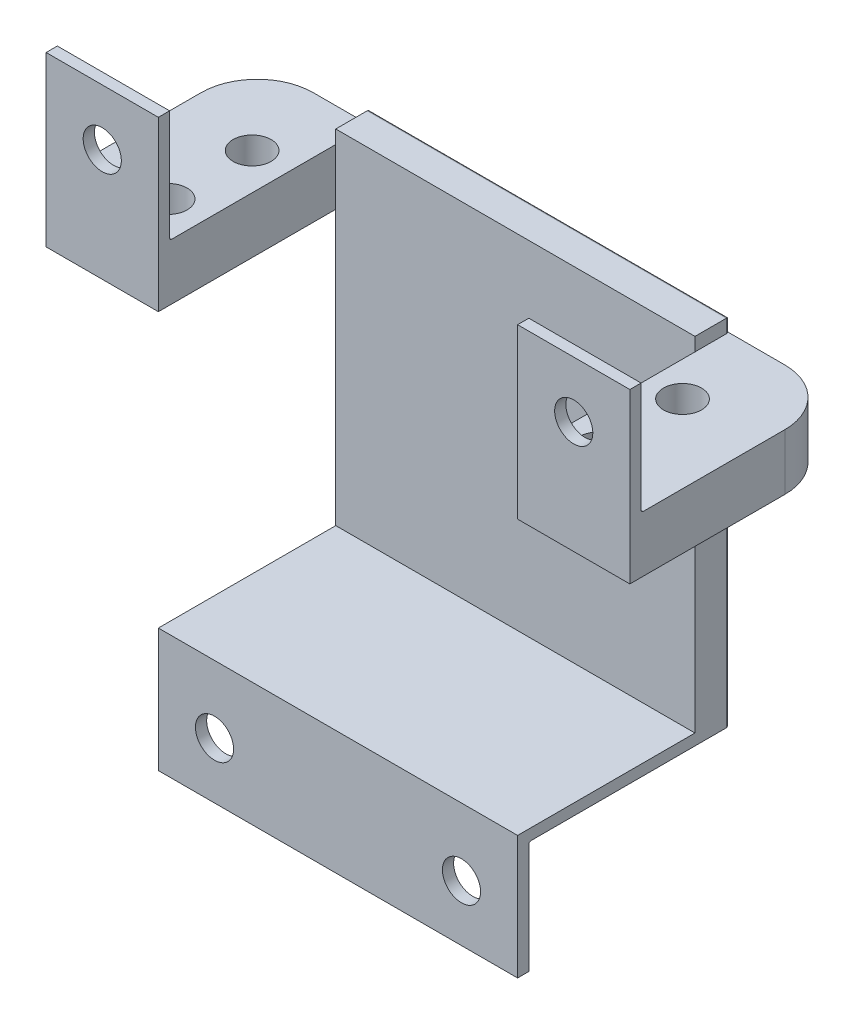
SolidWorks part; units mm, degrees
ref_plane "Front Plane" through (0, 0, 0) normal (0, 0, 1) x (1, 0, 0)
ref_plane "Top Plane" through (0, 0, 0) normal (0, 1, 0) x (1, 0, 0)
ref_plane "Right Plane" through (0, 0, 0) normal (1, 0, 0) x (0, 0, -1)
sketch "Sketch1" plane through (0, 0, 0) normal (0, 1, 0) x (1, 0, 0)
  line L1 (0, 0) -> (12.7, 0)
  line L2 (0, 0) -> (0, 18.796)
  line L3 (0, 18.796) -> (12.7, 18.796)
  line L4 (12.7, 0) -> (12.7, 18.796)
  dimension "D1" = 12.7
  dimension "D2" = 18.796
extrude "Boss-Extrude1" add sketch "Sketch1" along normal blind 6.35
sketch "Sketch2" plane through (0, 6.35, 0) normal (0, 1, 0) x (1, 0, 0)
  line L2 (0, 0) -> (12.7, 0) construction
  line L3 (6.35, 0) -> (8.89, 0) construction
  line L6 (12.7, 18.796) -> (0, 18.796) construction
  line L8 (0, 18.796) -> (0, 0) construction
  circle A9 centre (8.5526, 14.75) radius 2.15
  circle A10 centre (8.5526, 5.25) radius 2.15
  dimension "D1" = 4.3
  dimension "D2" = 4.3
  dimension "D4" = 4.046
  dimension "D3" = 9.5
  dimension "D5" = 8.5526
  dimension "D6" = 8.5526
extrude "Cut-Extrude1" cut sketch "Sketch2" against normal up to surface (6.35 mm away) contours A9 | A10 up to face at (6.35, 0, -9.398)
sketch "Sketch3" plane through (0, 0, -18.796) normal (0, 0, -1) x (-1, 0, 0)
  line L6 (0, 0) -> (-66.04, 0)
  line L7 (0, 0) -> (0, 6.35)
  line L8 (0, 6.35) -> (-66.04, 6.35)
  line L9 (-66.04, 0) -> (-66.04, 6.35)
  dimension "D1" = 6.35
  dimension "D2" = 66.04
extrude "Boss-Extrude2" add sketch "Sketch3" along normal blind 5.08
sketch "Sketch4" plane through (0, 0, -23.876) normal (0, 0, -1) x (-1, 0, 0)
  line L0 (0, 6.35) -> (-66.04, 6.35) construction
  line L1 (-53.34, 6.35) -> (-12.7, 6.35)
  line L2 (-53.34, 6.35) -> (-53.34, 7.874)
  line L3 (-53.34, 7.874) -> (-12.7, 7.874)
  line L4 (-12.7, 6.35) -> (-12.7, 7.874)
  dimension "D1" = 1.524
  dimension "D2" = 40.64
  dimension "D3" = 12.7
extrude "Boss-Extrude5" add sketch "Sketch4" against normal blind 3.81
sketch "Sketch9" plane through (0, 0, -23.876) normal (0, 0, -1) x (-1, 0, 0)
  line L9 (-12.7, 7.874) -> (-12.7, 0) construction
  line L11 (-12.7, 0) -> (-53.34, 0)
  line L12 (-12.7, 0) -> (-12.7, -30.988)
  line L13 (-12.7, -30.988) -> (-53.34, -30.988)
  line L14 (-53.34, 0) -> (-53.34, -30.988)
  dimension "D1" = 40.64
  dimension "D2" = 30.988
extrude "Boss-Extrude6" add sketch "Sketch9" against normal blind 3.81
sketch "Sketch10" plane through (0, 0, -18.796) normal (0, 0, 1) x (1, 0, 0)
  line L7 (12.7, 6.35) -> (66.04, 6.35)
  line L8 (12.7, 6.35) -> (12.7, 0)
  line L9 (12.7, 0) -> (66.04, 0)
  line L10 (66.04, 6.35) -> (66.04, 0)
extrude "Cut-Extrude3" cut sketch "Sketch10" against normal up to surface (1.27 mm away) up to face at (33.02, 7.112, -20.066)
sketch "Sketch11" plane through (0, 0, 0) normal (0, 0, 1) x (1, 0, 0)
  line L17 (12.7, 0) -> (0, 0)
  line L18 (12.7, 0) -> (12.7, 19.05)
  line L19 (12.7, 19.05) -> (0, 19.05)
  line L20 (0, 0) -> (0, 19.05)
  dimension "D1" = 19.05
  dimension "D2" = 12.7
extrude "Boss-Extrude7" add sketch "Sketch11" against normal blind 1.27
sketch "Sketch16" plane through (0, 0, -1.27) normal (0, 0, -1) x (-1, 0, 0)
  line L0 (-6.35, 6.35) -> (-6.35, 19.05) construction
  line L3 (-12.7, 6.35) -> (0, 6.35) construction
  line L4 (-12.7, 19.05) -> (0, 19.05) construction
  circle A1 centre (-6.35, 12.7) radius 2.159
  dimension "D1" = 4.318
extrude "Cut-Extrude5" cut sketch "Sketch16" against normal up to surface (1.27 mm away) up to face at (6.35, 9.525, 0)
sketch "Sketch17" plane through (0, 0, -23.876) normal (0, 0, -1) x (-1, 0, 0)
  line L1 (-53.34, 6.35) -> (-66.04, 6.35)
  line L2 (-53.34, 6.35) -> (-53.34, 0)
  line L3 (-53.34, 0) -> (-66.04, 0)
  line L4 (-66.04, 6.35) -> (-66.04, 0)
extrude "Boss-Extrude8" add sketch "Sketch17" against normal blind 23.876
sketch "Sketch20" plane through (0, 6.35, 0) normal (0, 1, 0) x (1, 0, 0)
  line L0 (53.34, 23.876) -> (66.04, 23.876) construction
  line L1 (53.34, 0) -> (66.04, 0) construction
  line L2 (53.34, 0) -> (53.34, 20.066) construction
  circle A4 centre (57.2474, 14.75) radius 2.15
  circle A5 centre (57.2474, 5.25) radius 2.15
  dimension "D1" = 4.3
  dimension "D2" = 4.3
  dimension "D3" = 9.5
  dimension "D4" = 9.126
  dimension "D5" = 5.25
  dimension "D6" = 3.9074
extrude "Cut-Extrude6" cut sketch "Sketch20" against normal up to surface (6.35 mm away) contours A4 | A5 up to face at (58.42, 0, -13.5636)
sketch "Sketch21" plane through (0, 0, 0) normal (0, 0, 1) x (1, 0, 0)
  line L5 (66.04, 0) -> (53.34, 0)
  line L6 (66.04, 0) -> (66.04, 19.05)
  line L7 (66.04, 19.05) -> (53.34, 19.05)
  line L8 (53.34, 0) -> (53.34, 19.05)
  dimension "D1" = 12.7
  dimension "D2" = 19.05
extrude "Boss-Extrude9" add sketch "Sketch21" against normal blind 1.27
sketch "Sketch22" plane through (0, 0, -1.27) normal (0, 0, -1) x (-1, 0, 0)
  line L0 (-59.69, 19.05) -> (-59.69, 6.35) construction
  line L3 (-66.04, 19.05) -> (-53.34, 19.05) construction
  line L4 (-66.04, 6.35) -> (-53.34, 6.35) construction
  circle A1 centre (-59.69, 12.7) radius 2.159
  dimension "D1" = 4.318
extrude "Cut-Extrude7" cut sketch "Sketch22" against normal up to surface (1.27 mm away) contours A1 up to face at (59.69, 9.525, 0)
sketch "Sketch23" plane through (0, -30.988, 0) normal (0, -1, 0) x (1, 0, 0)
  line L1 (53.34, -23.876) -> (12.7, -23.876)
  line L2 (53.34, -23.876) -> (53.34, 0)
  line L3 (53.34, 0) -> (12.7, 0)
  line L4 (12.7, -23.876) -> (12.7, 0)
  dimension "D1" = 40.64
  dimension "D2" = 23.876
extrude "Boss-Extrude10" add sketch "Sketch23" along normal blind 1.27
sketch "Sketch24" plane through (0, 0, 0) normal (0, 0, 1) x (1, 0, 0)
  line L1 (12.7, -30.988) -> (53.34, -30.988)
  line L2 (12.7, -30.988) -> (12.7, -44.958)
  line L3 (12.7, -44.958) -> (53.34, -44.958)
  line L4 (53.34, -30.988) -> (53.34, -44.958)
  dimension "D1" = 40.64
  dimension "D2" = 13.97
extrude "Boss-Extrude11" add sketch "Sketch24" against normal blind 1.27
sketch "Sketch25" plane through (0, 0, -1.27) normal (0, 0, -1) x (-1, 0, 0)
  line L0 (-53.34, -44.958) -> (-40.64, -44.958) construction
  line L1 (-12.7, -44.958) -> (-53.34, -44.958) construction
  line L2 (-40.64, -44.958) -> (-40.64, -32.258) construction
  line L3 (-12.7, -32.258) -> (-53.34, -32.258) construction
  line L4 (-40.64, -32.258) -> (-53.34, -44.958) construction
  line L5 (-25.4, -32.258) -> (-25.4, -44.958) construction
  line L6 (-53.34, -32.258) -> (-12.7, -32.258) construction
  line L7 (-25.4, -44.958) -> (-12.7, -44.958) construction
  line L8 (-12.7, -44.958) -> (-25.4, -32.258) construction
  circle A0 centre (-46.99, -38.608) radius 2.159
  circle A1 centre (-19.05, -38.608) radius 2.159
  dimension "D2" = 4.318
  dimension "D4" = 4.318
  dimension "D1" = 12.7
  dimension "D3" = 12.7
extrude "Cut-Extrude8" cut sketch "Sketch25" against normal up to surface (1.27 mm away) contours A0 | A1 up to face at (33.02, -37.973, 0)
fillet "Fillet4" radius 6.35 2 edges at (0, 3.175, -23.876) (66.04, 3.175, -23.876)
fillet "Fillet5" radius 0.254 9 edges at (33.02, -32.258, -1.27) (59.69, 6.35, -1.27) (6.35, 6.35, -1.27) (12.7, -16.129, -23.876) (33.02, -32.258, -23.876) (53.34, -16.129, -23.876) (33.02, 7.874, -23.876) (53.34, 7.112, -23.876) (12.7, 7.112, -23.876)
